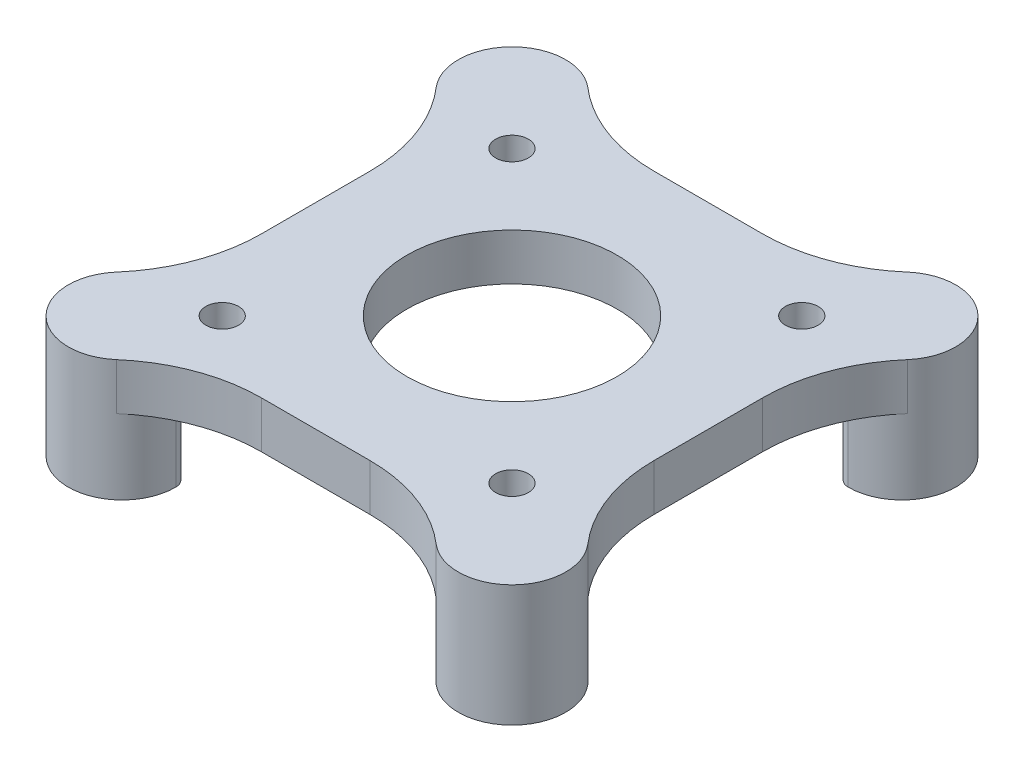
SolidWorks part; units mm, degrees
ref_plane "Front" through (0, 0, 0) normal (0, 0, 1) x (1, 0, 0)
ref_plane "Top" through (0, 0, 0) normal (0, 1, 0) x (1, 0, 0)
ref_plane "Right" through (0, 0, 0) normal (1, 0, 0) x (0, 0, -1)
sketch "草图1" plane through (0, 0, 0) normal (0, 1, 0) x (1, 0, 0)
  line L0 (-25.1989, 0) -> (25.3384, 0) construction
  line L1 (0, 24.0535) -> (0, -21.6423) construction
  line L3 (-21, -21) -> (21, -21)
  line L4 (-21, -21) -> (-21, 21)
  line L5 (-21, 21) -> (21, 21)
  line L6 (21, -21) -> (21, 21)
  line L7 (-21, -21) -> (21, 21) construction
  line L8 (-21, 21) -> (21, -21) construction
  circle A0 centre (0, 0) radius 11.25
  circle A1 centre (15.5, 15.5) radius 1.75
  circle A2 centre (15.5, -15.5) radius 1.75
  circle A3 centre (-15.5, -15.5) radius 1.75
  circle A4 centre (-15.5, 15.5) radius 1.75
  point P22 (0, 0)
  dimension "D1" = 22.5
  dimension "D4" = 15.5
  dimension "D6" = 3.5
  dimension "D2" = 42
  dimension "D3" = 42
  dimension "D5" = 4
extrude "凸台-拉伸1" add sketch "草图1" along normal blind 5
sketch "草图2" plane through (0, 0, 0) normal (0, 1, 0) x (1, 0, 0)
  line L0 (0, 0) -> (28.6077, -28.6077) construction
  line L1 (-5.8022, -21) -> (-21, -21)
  line L2 (-21, -21) -> (21, -21) construction
  line L3 (21, -5.8022) -> (21, -21)
  line L4 (21, -21) -> (5.8022, -21)
  line L5 (-21, -21) -> (-21, -5.8022)
  line L6 (-21, 5.8022) -> (-21, 21)
  line L7 (-21, 21) -> (-5.8022, 21)
  line L8 (5.8022, 21) -> (21, 21)
  line L9 (21, 21) -> (21, 5.8022)
  circle A0 centre (20.8597, -20.8597) radius 3.25 construction
  circle A1 centre (20.8597, -20.8597) radius 5.75 construction
  arc A2 (5.8022, -21) -> (17.0975, -25.2081) centre (5.8022, -38.2635) cw
  arc A3 (21, -5.8022) -> (25.2081, -17.0975) centre (38.2635, -5.8022) ccw
  arc A4 (25.2081, -17.0975) -> (17.0975, -25.2081) centre (20.8597, -20.8597) cw
  arc A5 (-5.8022, -21) -> (-17.0975, -25.2081) centre (-5.8022, -38.2635) ccw
  arc A6 (-17.0975, -25.2081) -> (-25.2081, -17.0975) centre (-20.8597, -20.8597) cw
  arc A7 (-21, -5.8022) -> (-25.2081, -17.0975) centre (-38.2635, -5.8022) cw
  arc A8 (-21, 5.8022) -> (-25.2081, 17.0975) centre (-38.2635, 5.8022) ccw
  arc A9 (-25.2081, 17.0975) -> (-17.0975, 25.2081) centre (-20.8597, 20.8597) cw
  arc A10 (-5.8022, 21) -> (-17.0975, 25.2081) centre (-5.8022, 38.2635) cw
  arc A11 (5.8022, 21) -> (17.0975, 25.2081) centre (5.8022, 38.2635) ccw
  arc A12 (17.0975, 25.2081) -> (25.2081, 17.0975) centre (20.8597, 20.8597) cw
  arc A13 (21, 5.8022) -> (25.2081, 17.0975) centre (38.2635, 5.8022) cw
  point P47 (0, 0)
  dimension "D1" = 6.5
  dimension "D3" = 2.5
  dimension "D2" = 29.5
extrude "凸台-拉伸2" add sketch "草图2" along normal blind 5
sketch "草图3" plane through (0, 0, 0) normal (0, -1, 0) x (1, 0, 0)
  line L0 (0, 0) -> (29.9149, 29.9149) construction
  line L2 (-7.1544, 0) -> (30.4001, 0) construction
  circle A0 centre (20.8597, 20.8597) radius 3.1 construction
  arc A1 (20.8597, 15.1097) -> (15.1097, 20.8597) centre (20.8597, 20.8597) ccw
  arc A2 (20.8597, 17.7597) -> (20.8597, 15.1097) centre (20.8597, 16.4347) ccw
  arc A3 (17.7597, 20.8597) -> (15.1097, 20.8597) centre (16.4347, 20.8597) cw
  arc A4 (17.7597, 20.8597) -> (20.8597, 17.7597) centre (20.8597, 20.8597) cw
  arc A5 (15.1097, 20.8597) -> (20.8597, 15.1097) centre (20.8597, 20.8597) ccw construction
  arc A6 (15.1097, -20.8597) -> (20.8597, -15.1097) centre (20.8597, -20.8597) ccw
  arc A7 (17.7597, -20.8597) -> (15.1097, -20.8597) centre (16.4347, -20.8597) ccw
  arc A8 (20.8597, -17.7597) -> (20.8597, -15.1097) centre (20.8597, -16.4347) cw
  arc A9 (20.8597, -17.7597) -> (17.7597, -20.8597) centre (20.8597, -20.8597) cw
  circle A10 centre (20.8597, -20.8597) radius 3.1 construction
  arc A11 (20.8597, -15.1097) -> (15.1097, -20.8597) centre (20.8597, -20.8597) ccw construction
  arc A12 (-20.8597, -15.1097) -> (-15.1097, -20.8597) centre (-20.8597, -20.8597) ccw
  arc A13 (-20.8597, -17.7597) -> (-20.8597, -15.1097) centre (-20.8597, -16.4347) ccw
  arc A14 (-17.7597, -20.8597) -> (-15.1097, -20.8597) centre (-16.4347, -20.8597) cw
  arc A15 (-17.7597, -20.8597) -> (-20.8597, -17.7597) centre (-20.8597, -20.8597) cw
  circle A16 centre (-20.8597, -20.8597) radius 3.1 construction
  arc A17 (-15.1097, -20.8597) -> (-20.8597, -15.1097) centre (-20.8597, -20.8597) ccw construction
  arc A18 (-15.1097, 20.8597) -> (-20.8597, 15.1097) centre (-20.8597, 20.8597) ccw
  arc A19 (-17.7597, 20.8597) -> (-15.1097, 20.8597) centre (-16.4347, 20.8597) ccw
  arc A20 (-20.8597, 17.7597) -> (-20.8597, 15.1097) centre (-20.8597, 16.4347) cw
  arc A21 (-20.8597, 17.7597) -> (-17.7597, 20.8597) centre (-20.8597, 20.8597) cw
  circle A22 centre (-20.8597, 20.8597) radius 3.1 construction
  arc A23 (-20.8597, 15.1097) -> (-15.1097, 20.8597) centre (-20.8597, 20.8597) ccw construction
  point P44 (0, 0)
  dimension "D1" = 6.2
  dimension "D3" = 45
  dimension "D2" = 29.5
  dimension "D4" = 4
extrude "凸台-拉伸3" add sketch "草图3" along normal blind 8
